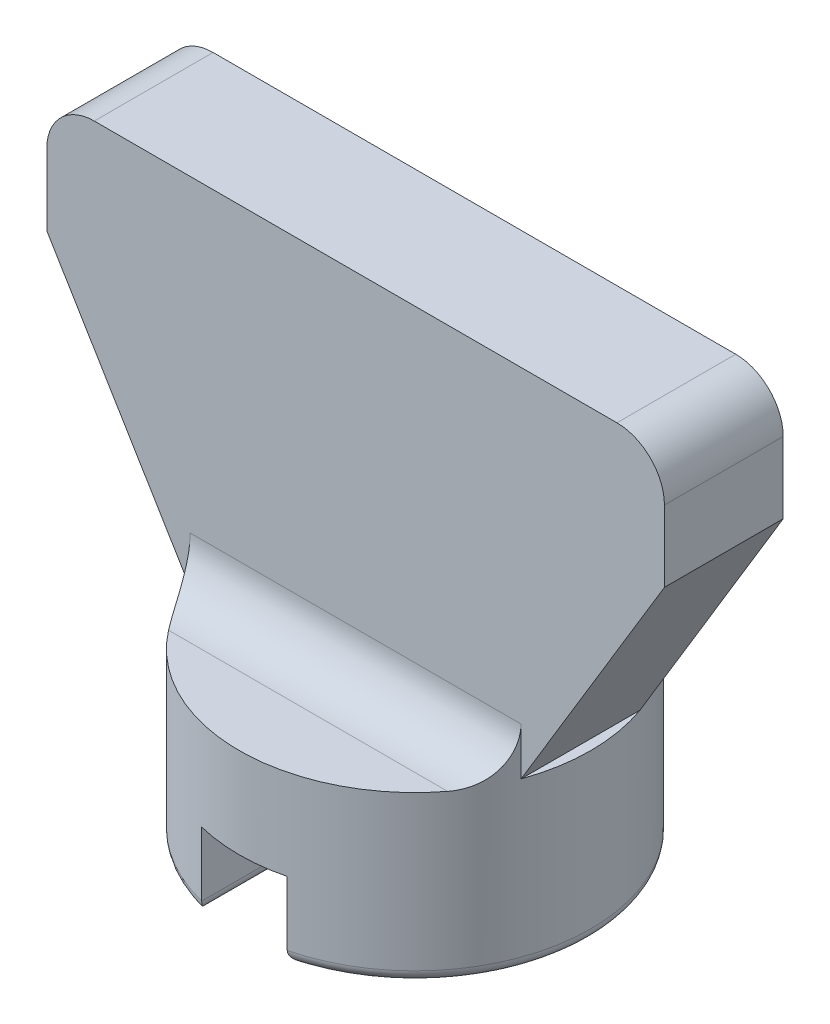
SolidWorks part; units mm, degrees
ref_plane "前视基准面" through (0, 0, 0) normal (0, 0, 1) x (1, 0, 0)
ref_plane "上视基准面" through (0, 0, 0) normal (0, 1, 0) x (1, 0, 0)
ref_plane "右视基准面" through (0, 0, 0) normal (1, 0, 0) x (0, 0, -1)
sketch "Sketch1" plane through (0, 0, 0) normal (0, 1, 0) x (1, 0, 0)
  circle A0 centre (0, 0) radius 7.4
  dimension "D1" = 14.8
extrude "Boss-Extrude1" add sketch "Sketch1" along normal blind 7
sketch "Sketch2" plane through (0, 0, 0) normal (0, -1, 0) x (1, 0, 0)
  line L1 (-1.8, 8.0374) -> (1.8, 8.0374)
  line L2 (-1.8, 8.0374) -> (-1.8, -8.2904)
  line L3 (-1.8, -8.2904) -> (1.8, -8.2904)
  line L4 (1.8, 8.0374) -> (1.8, -8.2904)
  point P7 (-0.648, 0.1802)
  dimension "D1" = 1.8
  dimension "D2" = 1.8
extrude "Cut-Extrude1" cut sketch "Sketch2" against normal blind 3.2
fillet "Fillet1" radius 0.5 4 edges at (-1.8, 0, 0) (1.8, 0, 0) (7.4, 0, 0) (-7.4, 0, 0)
sketch "Sketch3" plane through (0, 7, 0) normal (0, 1, 0) x (1, 0, 0)
  line L1 (-13, 2.5) -> (13, 2.5)
  line L2 (-13, 2.5) -> (-13, -2.5)
  line L3 (-13, -2.5) -> (13, -2.5)
  line L4 (13, 2.5) -> (13, -2.5)
  dimension "D1" = 2.5
  dimension "D2" = 2.5
  dimension "D3" = 13
  dimension "D4" = 13
extrude "Boss-Extrude2" add sketch "Sketch3" along normal blind 15
sketch "Sketch4" plane through (0, 0, 2.5) normal (0, 0, 1) x (1, 0, 0)
  line L0 (-6.9649, 7) -> (-13, 17)
  line L1 (-13, 22) -> (-13, 7) construction
  line L2 (-13, 17) -> (-13, 7)
  line L3 (-13, 7) -> (-6.9649, 7)
  line L4 (6.9649, 7) -> (13, 17)
  line L5 (13, 22) -> (13, 7) construction
  line L6 (13, 17) -> (13, 7)
  line L7 (13, 7) -> (6.9649, 7)
  dimension "D1" = 10
  dimension "D2" = 10
extrude "Cut-Extrude2" cut sketch "Sketch4" against normal through all
fillet "Fillet2" radius 2 2 edges at (-13, 22, 0) (13, 22, 0)
fillet "Fillet3" radius 2 2 edges at (0, 7, -2.5) (0, 7, 2.5)
